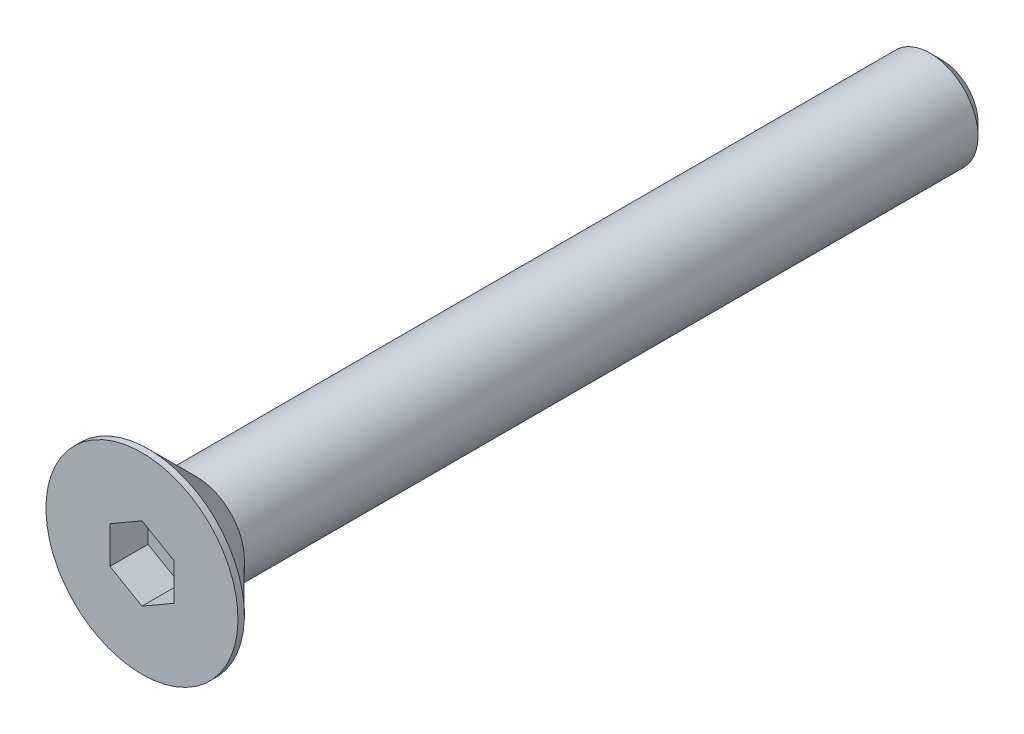
SolidWorks part; units mm, degrees
ref_plane "Front" through (0, 0, 0) normal (0, 0, 1) x (1, 0, 0)
ref_plane "Top" through (0, 0, 0) normal (0, 1, 0) x (1, 0, 0)
ref_plane "Right" through (0, 0, 0) normal (1, 0, 0) x (0, 0, -1)
sketch "Sketch1" plane through (0, 0, 0) normal (1, 0, 0) x (0, 0, -1)
  line L0 (0, 3) -> (0.2, 3) construction
  line L1 (0.2, 3) -> (1.7, 1.5) construction
  line L2 (0, 1.5) -> (25, 1.5)
  line L3 (25, 1.5) -> (25, 0)
  line L4 (25, 0) -> (0, 0)
  line L5 (0, 0) -> (0, 3) construction
  line L6 (0, 3) -> (0, -3) construction
  line L7 (25, 1.5) -> (25, -1.5) construction
  line L8 (0, -3) -> (0.2, -3) construction
  line L9 (0.2, -3) -> (1.7, -1.5) construction
  line L11 (0, 1.5) -> (0, 0)
  line L12 (1.7, 1.5) -> (1.7, 0) construction
revolve "Revolve1" add sketch "Sketch1" angle 360 mid plane about L4
sketch "Sketch3" plane through (0, 0, -25) normal (0, 0, -1) x (-1, 0, 0)
  circle A0 centre (0, 0) radius 1.5
curve "Helix/Spiral1" [suppressed] pitch 0.5 height 25 turns 50
sketch "Sketch2" plane through (0, 0, 0) normal (1, 0, 0) x (0, 0, -1)
  line L0 (25, 1.5) -> (25.4375, 1.5)
  line L1 (25.4375, 1.5) -> (25.25, 1.1752)
  line L2 (25.25, 1.1752) -> (25.1875, 1.1752)
  line L3 (25.1875, 1.1752) -> (25, 1.5)
  line L4 (25.0938, 1.3376) -> (25.3438, 1.3376) construction
  dimension "D1" = 60
  dimension "D2" = 0.0625
  dimension "D3" = 0.25
chamfer "Chamfer1" distance 0.375 angle 45 1 edges at (0, 1.5, -25)
sweep "Cut-Sweep1" [suppressed] cut profiles "Sketch2" path "Helix/Spiral1"
sketch "Sketch7" plane through (0, 0, 0) normal (1, 0, 0) x (0, 0, -1)
  line L0 (0, 3) -> (0.2, 3) construction
  line L1 (0.2, 3) -> (1.7, 1.5) construction
  line L2 (0, 3) -> (0.2, 3)
  line L3 (0.2, 3) -> (1.7, 1.5)
  line L4 (1.7, 1.5) -> (1.7, 0) construction
  line L5 (1.7, 1.5) -> (1.7, 0)
  line L7 (0, 0) -> (0, 3) construction
  line L8 (0, 0) -> (0, 3)
  line L9 (0, 0) -> (1.7, 0)
  line L10 (3.3, 0) -> (-3.3, 0) construction
revolve "Revolve2" add sketch "Sketch7" angle 360 mid plane about L9
ref_plane "Plane1" through (0, 0, -1.7) normal (0, 0, 1) x (1, 0, 0)
sketch "Sketch8" plane through (0, 0, -1.7) normal (0, 0, 1) x (1, 0, 0)
  circle A0 centre (0, 0) radius 1.5
extrude "Boss-Extrude1" add sketch "Sketch8" against normal through all draft 45
sketch "Sketch5" plane through (0, 0, 0) normal (0, 0, 1) x (1, 0, 0)
  line L1 (1, -0.5774) -> (1, 0.5774)
  line L2 (1, 0.5774) -> (0, 1.1547)
  line L3 (0, 1.1547) -> (-1, 0.5774)
  line L4 (-1, 0.5774) -> (-1, -0.5774)
  line L5 (-1, -0.5774) -> (0, -1.1547)
  line L6 (0, -1.1547) -> (1, -0.5774)
  circle A0 centre (0, 0) radius 1 construction
  dimension "Hex" = 2
extrude "Cut-Extrude2" cut sketch "Sketch5" against normal blind 1.19
sketch "Sketch6" plane through (0, 0, 0) normal (0, 0, 1) x (1, 0, 0)
  circle A0 centre (0, 0) radius 1.1547
extrude "Cut-Extrude3" [suppressed] cut sketch "Sketch6" against normal blind 1.19 draft 45
sketch "Sketch9" [suppressed] plane through (0, 0, -5.5) normal (0, 0, 1) x (1, 0, 0)
  circle A1 centre (0, 0) radius 5
  circle A2 centre (0, 0) radius 5
  point P0 (0, 5)
  dimension "D1" = 0
extrude "Boss-Extrude2" [suppressed] add sketch "Sketch9" against normal offset from surface (18.5 mm away) 26
fillet "Fillet1" [suppressed] radius 0.3
sketch "Sketch10" plane through (0, 0, 0) normal (1, 0, 0) x (0, 0, -1)
  line L0 (25, 1.5) -> (25, -1.5) construction
  point P0 (24.25, -1.5)
  dimension "D1" = 0.75
equation "\"D3@Helix/Spiral1\" = \"Lg@Sketch1\""
equation "\"D2@Sketch2\" = \"D4@Helix/Spiral1\" * .125"
equation "\"D3@Sketch2\" = \"D4@Helix/Spiral1\" * .5"
equation "\"D1@Chamfer1\" = \"D4@Helix/Spiral1\" * .75"
equation "\"D1@Cut-Extrude2\" = \"Head Ht@Sketch1\" * .7"
equation "\"D1@Sketch10\" = \"D4@Helix/Spiral1\" * 1.5"
equation "\"D1@Cut-Extrude3\" = \"D1@Cut-Extrude2\""
equation "\"D1@Fillet1\" = \"Dia@Sketch1\" * .1"
